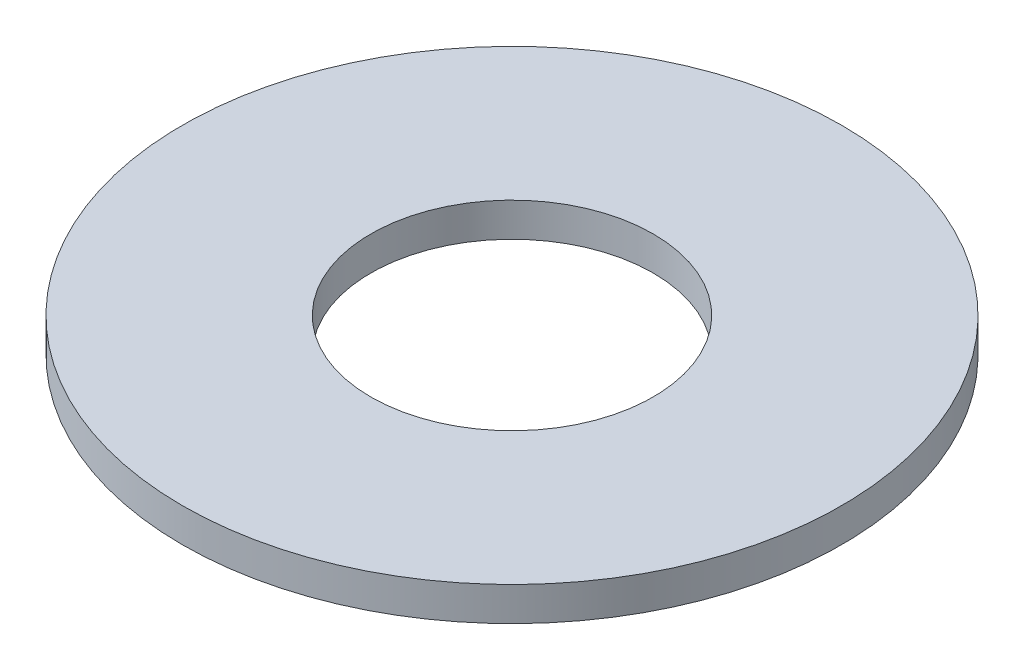
SolidWorks part; units mm, degrees
ref_plane "Front Plane" through (0, 0, 0) normal (0, 0, 1) x (1, 0, 0)
ref_plane "Top Plane" through (0, 0, 0) normal (0, 1, 0) x (1, 0, 0)
ref_plane "Right Plane" through (0, 0, 0) normal (1, 0, 0) x (0, 0, -1)
sketch "Sketch1" plane through (0, 0, 0) normal (0, 1, 0) x (1, 0, 0)
  circle A0 centre (0, 0) radius 87.5
  dimension "FLANGE_OD" = 175
extrude "Boss-Extrude1" add sketch "Sketch1" along normal blind 9
sketch "Sketch2" plane through (0, 0, 0) normal (0, 1, 0) x (1, 0, 0)
  circle A0 centre (0, 0) radius 37.5
  dimension "BORE_D" = 75
extrude "Cut-Extrude1" cut sketch "Sketch2" along normal through all
sketch "Sketch3" plane through (0, 9, 0) normal (0, 1, 0) x (1, 0, 0)
  circle A0 centre (0, 0) radius 26.8138 construction
  circle A1 centre (-26.8138, 0) radius 5.667
  dimension "BOLT_D" = 11.334
  dimension "BOLT_PCD" = 53.6276
extrude "Cut-Extrude2" cut sketch "Sketch3" against normal blind 6.9853 rebuild error yes
pattern_circular "CirPattern1" count 6 over 360 rebuild error yes
